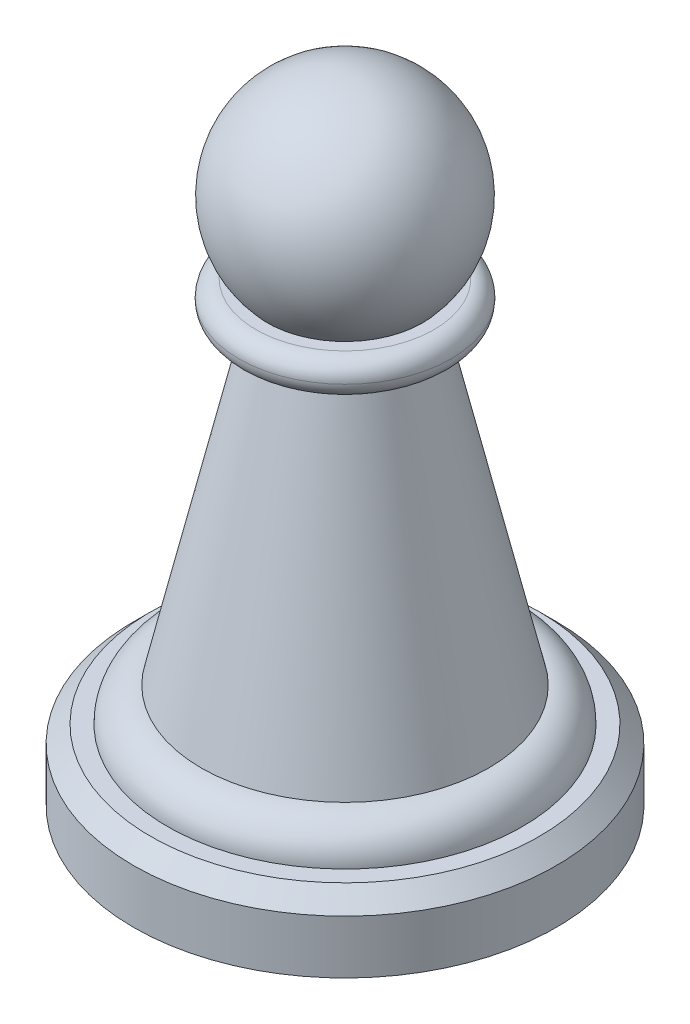
SolidWorks part; units mm, degrees
ref_plane "Front Plane" through (0, 0, 0) normal (0, 0, 1) x (1, 0, 0)
ref_plane "Top Plane" through (0, 0, 0) normal (0, 1, 0) x (1, 0, 0)
ref_plane "Right Plane" through (0, 0, 0) normal (1, 0, 0) x (0, 0, -1)
sketch "Sketch2" plane through (0, 0, 0) normal (0, 0, 1) x (1, 0, 0)
  line L0 (0, 0) -> (0, 28.575) construction
  line L1 (-6.477, 3.175) -> (-6.477, 4.699) construction
  line L2 (0, 0) -> (-9.525, 0)
  line L4 (-8.001, 3.175) -> (-9.525, 3.175)
  line L5 (-9.525, 0) -> (-9.525, 3.175)
  line L8 (-6.477, 4.699) -> (-8.001, 4.699)
  line L9 (-8.001, 3.175) -> (-8.001, 4.699)
  line L10 (-3.175, 19.05) -> (-9.525, 19.05) construction
  line L11 (-6.477, 4.699) -> (-3.175, 19.05)
  line L12 (0, 0) -> (0, 28.575)
  line L13 (-3.175, 19.05) -> (-4.7752, 19.05)
  line L15 (-3.4919, 20.574) -> (-4.7752, 20.574)
  line L16 (-4.7752, 19.05) -> (-4.7752, 20.574)
  line L17 (0, 19.05) -> (-9.525, 19.05) construction
  arc A0 (0, 28.575) -> (-3.4919, 20.574) centre (0, 23.8125) ccw
  dimension "D11" = 9.525
  dimension "D1" = 28.575
  dimension "D2" = 9.525
  dimension "D3" = 3.175
  dimension "D4" = 1.524
  dimension "D5" = 1.524
  dimension "D9" = 1.524
  dimension "D6" = 1.524
  dimension "D7" = 19.05
revolve "Revolve1" add sketch "Sketch2" angle 360 about L12
chamfer "Chamfer1" distance 0.762 angle 45 1 edges at (0, 3.175, -9.525)
fillet "Fillet1" radius 1.524 1 edges at (0, 4.699, -8.001)
fillet "Fillet2" radius 0.762 2 edges at (0, 19.05, -4.7752) (0, 20.574, -4.7752)
